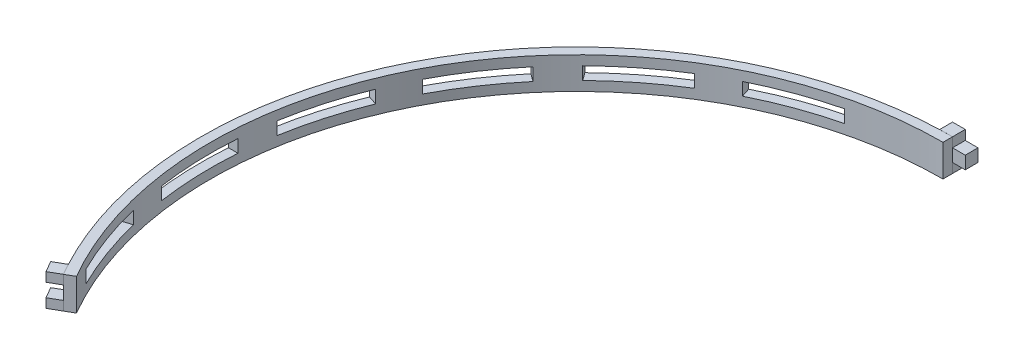
SolidWorks part; units mm, degrees
note: '?' marks a value the reader was unsure of.
ref_plane "Front Plane" through (0, 0, 0) normal (0, 0, 1) x (1, 0, 0)
ref_plane "Top Plane" through (0, 0, 0) normal (0, 1, 0) x (1, 0, 0)
ref_plane "Right Plane" through (0, 0, 0) normal (1, 0, 0) x (0, 0, -1)
sketch "Sketch1" plane through (0, 0, 0) normal (0, 1, 0) x (1, 0, 0)
  line L0 (118, 0) -> (115, 0) construction
  line L1 (0, 118) -> (0, -118)
  line L6 (0, 0) -> (-215.0076, 0) construction
  line L7 (0, 0) -> (-102.191, -59)
  line L9 (-102.191, -59) -> (-105.6551, -61)
  line L10 (-105.6551, -61) -> (-107.6551, -57.5359)
  line L11 (-107.6551, -57.5359) -> (-104.1323, -55.502)
  line L12 (-104.1323, -55.502) -> (-102.191, -59)
  line L13 (0, 118) -> (0, 122)
  line L14 (0, 122) -> (-4, 122)
  line L15 (-4, 122) -> (-4, 117.9322)
  line L16 (-4, 117.9322) -> (0, 118)
  circle A0 centre (0, 0) radius 115
  circle A1 centre (0, 0) radius 118
  dimension "D1" = 230
  dimension "D2" = 3
  dimension "D3" = 120
  dimension "D4" = 4
  dimension "D5" = 4
  dimension "D6" = 4
  dimension "D7" = 4
extrude "Boss-Extrude1" add sketch "Sketch1" along normal blind 10 contours L16 A1 L12 L7 A0 L1 | A1 L13 L14 L15 | A1 L11 L10 L9
ref_axis "Axis1" through (0, 10, 0) along (0, -1, 0)?
sketch "Sketch2" plane through (-105.6551, 0, 61) normal (-0.866, 0, 0.5) x (0.5, 0, 0.866)
  line L0 (-4, 10) -> (-4, 0) construction
  line L1 (-4, 7.1) -> (4, 7.1)
  line L2 (-4, 7.1) -> (-4, 2.9)
  line L3 (-4, 2.9) -> (4, 2.9)
  line L4 (4, 7.1) -> (4, 2.9)
  point P6 (-4, 5)
  point P7 (-4, 5)
  dimension "D1" = 4.2
  dimension "D2" = 8
extrude "Cut-Extrude1" cut sketch "Sketch2" against normal blind 4
sketch "Sketch3" plane through (0, 0, -122) normal (0, 0, -1) x (-1, 0, 0)
  line L0 (4, 10) -> (4, 0) construction
  line L1 (4, 3) -> (-4, 3)
  line L2 (4, 3) -> (4, 7)
  line L3 (4, 7) -> (-4, 7)
  line L4 (-4, 3) -> (-4, 7)
  point P6 (4, 5)
  point P7 (4, 5)
  dimension "D2" = 8
  dimension "D1" = 4
extrude "Boss-Extrude2" add sketch "Sketch3" against normal blind 4 contours L2 L1 L4 L3
sketch "Sketch4" plane through (0, 0, 0) normal (1, 0, 0) x (0, 0, -1)
  line L0 (-55.502, 0) -> (117.9322, 0) construction
  line L1 (8.3277, 7) -> (-16.6723, 7)
  line L2 (8.3277, 7) -> (8.3277, 3)
  line L3 (8.3277, 3) -> (-16.6723, 3)
  line L4 (-16.6723, 7) -> (-16.6723, 3)
  line L5 (117.9322, 10) -> (-55.502, 10) construction
  dimension "D1" = 3
  dimension "D2" = 3
  dimension "D3" = 25
extrude "Cut-Extrude2" cut sketch "Sketch4" against normal through all
pattern_circular "CirPattern4" count 5 every 18 about axis through (0, 0, 0) along (0, 1, 0) of "Cut-Extrude2"
equation "\"key_height\"= 4mm"
equation "\"slot_height\"= \"key_height\" + 0.2mm"
equation "\"D1@Sketch2\"=\"slot_height\""
equation "\"D1@Sketch3\"=\"key_height\""
